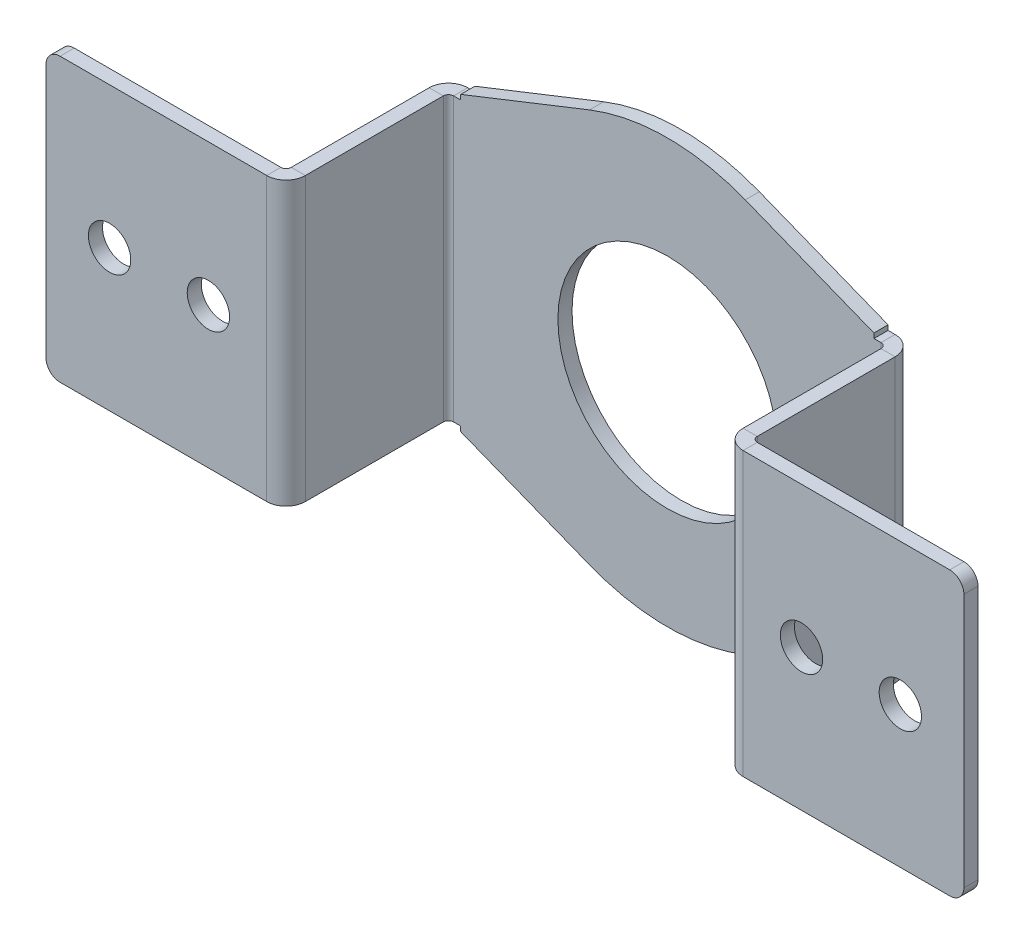
SolidWorks part; units mm, degrees
note: The reader was unsure of these and kept them because the rebuilt part matched: flange length of "Edge-Flange1", "Edge-Flange2".
material "1023 Carbon Steel Sheet (SS)"
ref_plane "Front Plane" through (0, 0, 0) normal (0, 0, 1) x (1, 0, 0)
ref_plane "Top Plane" through (0, 0, 0) normal (0, 1, 0) x (1, 0, 0)
ref_plane "Right Plane" through (0, 0, 0) normal (1, 0, 0) x (0, 0, -1)
sketch "Sketch1" plane through (0, 0, 0) normal (0, 0, 1) x (1, 0, 0)
  line L0 (0, 0) -> (-65, 0) construction
  line L2 (-31, 20) -> (-11.0341, 27.8971)
  line L3 (-31, -20) -> (-11.0341, -27.8971)
  line L4 (-31, 20) -> (-31, -20)
  line L5 (0, 0) -> (0, 30) construction
  line L6 (31, -20) -> (11.0341, -27.8971)
  line L7 (31, 20) -> (31, -20)
  line L8 (31, 20) -> (11.0341, 27.8971)
  circle A0 centre (0, 0) radius 15.5
  arc A1 (-11.0341, -27.8971) -> (11.0341, -27.8971) centre (0, 0) ccw
  arc A2 (11.0341, 27.8971) -> (-11.0341, 27.8971) centre (0, 0) ccw
  point P7 (-65, 0)
  point P13 (-31, 0)
  dimension "D1" = 31
  dimension "D2" = 60
  dimension "D3" = 40
  dimension "D5" = 31
base flange "Base-Flange1" sketch "Sketch1" thickness 2 reverse thickness direction no parameters "D1"=0.7366
edge flange "Edge-Flange1" sketch "Sketch8" flange profiles "Sketch8", "Sketch10" flange angle 90 flange length 23 flange position material outside bend radius 0.7366 thickness 2 relief rectangular parameters "D6"=10, "D8"=1
sketch "Sketch8" plane through (-31, 0, 0) normal (-1, 0, 0) x (0, -1, 0)
  line L2 (-20, 0) -> (-20, 21)
  line L3 (-20, 21) -> (20, 21)
  line L4 (20, 21) -> (20, 0)
  line L7 (-20, 0) -> (20, 0) construction
  line L8 (-20, 0) -> (20, 0)
sketch "Sketch10" plane through (31, 0, 0) normal (1, 0, 0) x (0, 1, 0)
  line L0 (-20, 0) -> (20, 0) construction
  line L1 (-20, 0) -> (20, 0)
  line L2 (-20, 0) -> (-20, 21)
  line L3 (-20, 21) -> (20, 21)
  line L4 (20, 21) -> (20, 0)
bend "EdgeBend1" bend radius 0.7366 bend angle 90 parameters "D5"=1
bend "EdgeBend2" bend radius 0.7366 bend angle 90 parameters "D5"=3
edge flange "Edge-Flange2" sketch "Sketch15" flange profiles "Sketch15", "Sketch16" flange angle 90 flange length 34 flange position material outside bend radius 0.7366 thickness 2 relief rectangular parameters "D6"=10, "D8"=1
sketch "Sketch15" plane through (-33, 0, 21) normal (0, 0, 1) x (0, 1, 0)
  line L2 (-20, 0) -> (-20, 32)
  line L3 (-20, 32) -> (20, 32)
  line L4 (20, 32) -> (20, 0)
  line L7 (-20, 0) -> (20, 0) construction
  line L8 (-20, 0) -> (20, 0)
sketch "Sketch16" plane through (33, 0, 21) normal (0, 0, 1) x (0, -1, 0)
  line L0 (-20, 0) -> (20, 0) construction
  line L1 (-20, 0) -> (20, 0)
  line L2 (-20, 0) -> (-20, 32)
  line L3 (-20, 32) -> (20, 32)
  line L4 (20, 32) -> (20, 0)
bend "EdgeBend3" bend radius 0.7366 bend angle 90 parameters "D5"=4
bend "EdgeBend4" bend radius 0.7366 bend angle 90 parameters "D5"=5
sketch "Sketch17" plane through (0, 0, 21) normal (0, 0, -1) x (-1, 0, 0)
  line L0 (0, 0) -> (65, 0) construction
  line L1 (65, 20) -> (65, -20) construction
  line L2 (0, 0) -> (0, 30) construction
  arc A0 (11.0341, 27.8971) -> (-11.0341, 27.8971) centre (0, 0) ccw construction
  circle A1 centre (56, 0) radius 3
  circle A2 centre (42, 0) radius 3
  circle A3 centre (-56, 0) radius 3
  circle A4 centre (-42, 0) radius 3
  dimension "D1" = 6
  dimension "D2" = 6
  dimension "D3" = 9
  dimension "D4" = 14
extrude "Cut-Extrude1" cut sketch "Sketch17" against normal blind 10 normal cut yes
fillet "Fillet1" radius 2 4 edges at (-65, -20, 22) (65, 20, 22) (65, -20, 22) (-65, 20, 22)
sketch "Bend-Lines1" [suppressed] plane through (0, 0, 0) normal (0, 1, 0) x (1, 0, 0)
sketch "Bounding-Box1" [suppressed] plane through (0, 0, 0) normal (0, 1, 0) x (1, 0, 0)
sheet metal parameters "Sheet-Metal1" thickness 2 parameters "D1"=0.7366
flat pattern "Flat-Pattern1" [suppressed]
sketch "Bend-Lines2" plane through (0, 0, 0) normal (0, 1, 0) x (1, 0, 0)
sketch3d "Bounding-Box2" [suppressed]
  line L0 (30.9987, 30.0007, 0) -> (-31.0001, 29.9992, 0) construction
  line L1 (31.0001, -29.9992, 0) -> (-30.9987, -30.0007, 0) construction
  line L2 (30.9987, 30.0007, 0) -> (31.0001, -29.9992, 0) construction
  line L3 (-31.0001, 29.9992, 0) -> (-30.9987, -30.0007, 0) construction
sheet metal parameters "Sheet-Metal2" thickness 2 parameters "D1"=0.7366
flat pattern "Flat-Pattern1"
sketch "Bend-Lines2" plane through (0, 0, 0) normal (0, 0, 1) x (1, 0, 0)
  line L0 (-31.6273, 25.4296) -> (-31.6273, -25.4296) construction
  line L1 (-31.6273, 25.4296) -> (-31.6273, -25.4296) construction
  line L2 (31.6273, -25.4296) -> (31.6273, 25.4296) construction
  line L3 (31.6273, -25.4296) -> (31.6273, 25.4296) construction
sketch3d "Bounding-Box2" [suppressed]
  line L0 (-51.2533, 30.0012, 0) -> (51.2548, 29.9987, 0) construction
  line L1 (-51.2548, -29.9987, 0) -> (51.2533, -30.0012, 0) construction
  line L2 (-51.2533, 30.0012, 0) -> (-51.2548, -29.9987, 0) construction
  line L3 (51.2548, 29.9987, 0) -> (51.2533, -30.0012, 0) construction
bend of the flat pattern "Flatten-<EdgeBend1>1"
bend of the flat pattern "Flatten-<EdgeBend2>1"
sheet metal parameters "Sheet-Metal3" thickness 2 parameters "D1"=0.7366
flat pattern "Flat-Pattern1"
sketch "Bend-Lines2" plane through (0, 0, 0) normal (0, 0, 1) x (1, 0, 0)
  line L0 (-31.6273, 25.4296) -> (-31.6273, -25.4296) construction
  line L1 (-31.6273, 25.4296) -> (-31.6273, -25.4296) construction
  line L2 (31.6273, -25.4296) -> (31.6273, 25.4296) construction
  line L3 (31.6273, -25.4296) -> (31.6273, 25.4296) construction
  line L4 (51.882, -25.4296) -> (51.882, 25.4296) construction
  line L5 (-51.882, 25.4296) -> (-51.882, -25.4296) construction
  line L6 (51.882, -25.4296) -> (51.882, 25.4296) construction
  line L7 (-51.882, 25.4296) -> (-51.882, -25.4296) construction
sketch3d "Bounding-Box2" [suppressed]
  line L0 (-84.508, 30.002, 0) -> (84.5094, 29.998, 0) construction
  line L1 (-84.5094, -29.998, 0) -> (84.508, -30.002, 0) construction
  line L2 (-84.508, 30.002, 0) -> (-84.5094, -29.998, 0) construction
  line L3 (84.5094, 29.998, 0) -> (84.508, -30.002, 0) construction
bend of the flat pattern "Flatten-<EdgeBend1>1"
bend of the flat pattern "Flatten-<EdgeBend2>1"
bend of the flat pattern "Flatten-<EdgeBend3>1"
bend of the flat pattern "Flatten-<EdgeBend4>1"
sheet metal parameters "Sheet-Metal4" thickness 2 parameters "D1"=0.7366
flat pattern "Flat-Pattern1"
sketch "Bend-Lines2" plane through (0, 0, 0) normal (0, 0, 1) x (1, 0, 0)
  line L0 (-31.6273, 20) -> (-31.6273, -20) construction
  line L1 (-31.6273, 20) -> (-31.6273, -20) construction
  line L2 (31.6273, -20) -> (31.6273, 20) construction
  line L3 (31.6273, -20) -> (31.6273, 20) construction
  line L4 (53.882, -20) -> (53.882, 20) construction
  line L5 (-53.882, 20) -> (-53.882, -20) construction
  line L6 (53.882, -20) -> (53.882, 20) construction
  line L7 (-53.882, 20) -> (-53.882, -20) construction
sketch3d "Bounding-Box2" [suppressed]
  line L0 (-86.5093, -30, 0) -> (86.5093, -30, 0) construction
  line L1 (-86.5093, 30, 0) -> (86.5093, 30, 0) construction
  line L2 (-86.5093, -30, 0) -> (-86.5093, 30, 0) construction
  line L3 (86.5093, -30, 0) -> (86.5093, 30, 0) construction
bend of the flat pattern "Flatten-<EdgeBend1>1"
bend of the flat pattern "Flatten-<EdgeBend2>1"
bend of the flat pattern "Flatten-<EdgeBend3>1"
bend of the flat pattern "Flatten-<EdgeBend4>1"
